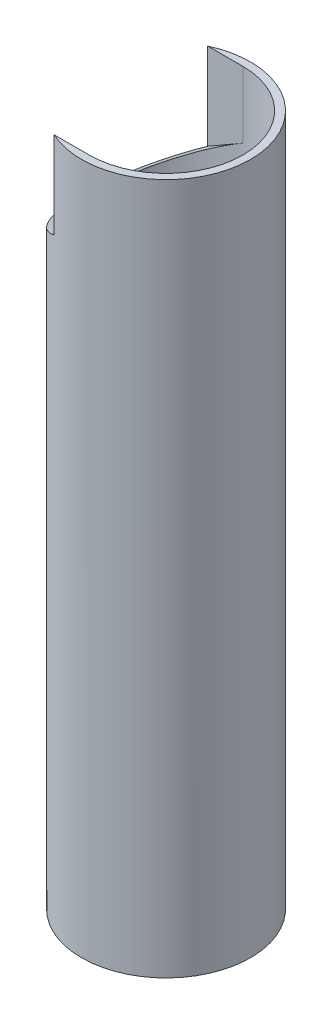
SolidWorks part; units mm, degrees
ref_plane "Front Plane" through (0, 0, 0) normal (0, 0, 1) x (1, 0, 0)
ref_plane "Top Plane" through (0, 0, 0) normal (0, 1, 0) x (1, 0, 0)
ref_plane "Right Plane" through (0, 0, 0) normal (1, 0, 0) x (0, 0, -1)
sketch "Sketch1" plane through (0, 0, 0) normal (0, 1, 0) x (1, 0, 0)
  line L2 (0, -20) -> (0, -22)
  line L3 (0, 20) -> (0, 22)
  circle A0 centre (0, 0) radius 20
  circle A2 centre (0, 0) radius 22
  dimension "D1" = 40
extrude "Boss-Extrude1" add sketch "Sketch1" along normal blind 180 contours A2 | A0
sketch "Sketch2" plane through (0, 180, 0) normal (0, 1, 0) x (1, 0, 0)
  line L0 (0, 0) -> (0, 10.719) construction
sketch "Sketch4" plane through (0, 0, 0) normal (0, 0, 1) x (1, 0, 0)
  line L0 (0, 180) -> (-14.244, 204.6713) construction
  line L1 (20, 180) -> (-20, 180) construction
  line L2 (0, 180) -> (11.4793, 180) construction
  dimension "D1" = 60
ref_plane "Plane1" through (77.9423, 45, 0) normal (0.866, 0.5, 0) x (0.5, -0.866, 0)
sketch "Sketch3" plane through (77.9423, 45, 0) normal (0.866, 0.5, 0) x (0.5, -0.866, 0)
  line L0 (-155.8846, -20) -> (-155.8846, 20) construction
  line L1 (-140.8846, 20) -> (-170.8846, 20)
  line L2 (-140.8846, 20) -> (-140.8846, -20)
  line L3 (-140.8846, -20) -> (-170.8846, -20)
  line L4 (-170.8846, 20) -> (-170.8846, -20)
  line L5 (-170.8846, 0) -> (-140.8846, 0) construction
  point P5 (-155.8846, 0)
  dimension "D1" = 30
  dimension "D2" = 40
extrude "Cut-Extrude1" cut sketch "Sketch3" against normal blind 63
extrude "Boss-Extrude2" add sketch "Sketch1<3>" against normal blind 30 from surface contours L2 A2 L3 A0 region at (14.49, 0, 14.49) starting at face at (8.2087, 180, 0)
sketch "Sketch1<3>" plane through (0, 0, 0) normal (0, 1, 0) x (1, 0, 0) same geometry as "Sketch1"
equation "\"in_d\"=40"
equation "\"D1@Sketch1\"=\"in_d\""
equation "\"pipe_thick\"=2"
equation "\"D2@Sketch1\"=\"pipe_thick\""
equation "\"rod_angle\"=20"
equation "\"rod_radius\"=33.5"
equation "\"rod_diameter\"=8"
equation "\"lin_bear_h\"=24"
equation "\"screw_radius\"=40"
equation "\"screw_angle\"=50"
equation "\"lin_bearing_d\"=15"
equation "\"drill_rod_pair\"=37"
equation "\"support_rod_w\"=50"
equation "\"vertical_slider_w\"=65"
equation "\"slope_angle\"=30"
equation "\"D1@Sketch4\"=90-\"slope_angle\""
equation "\"D2@Sketch3\"=\"in_d\""
